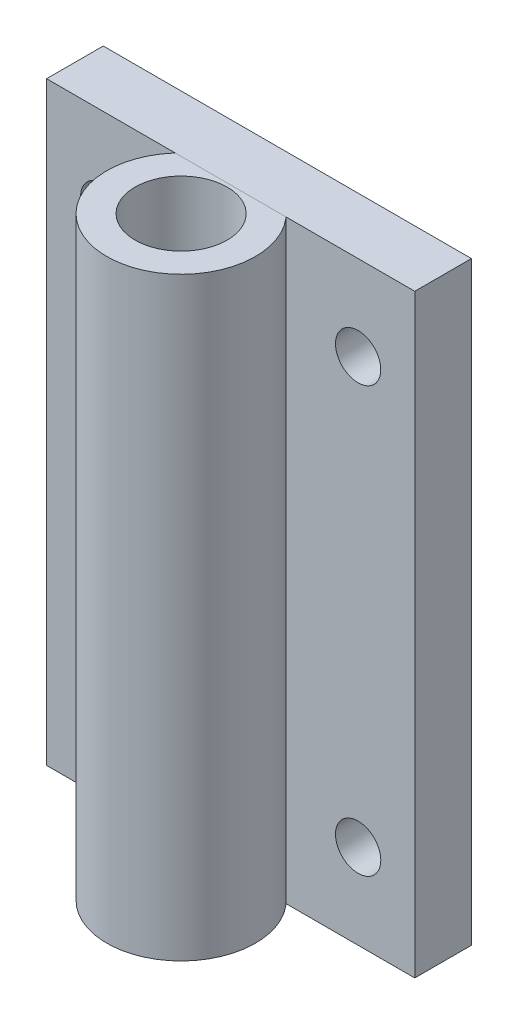
SolidWorks part; units mm, degrees
ref_plane "前视基准面" through (0, 0, 0) normal (0, 0, 1) x (1, 0, 0)
ref_plane "上视基准面" through (0, 0, 0) normal (0, 1, 0) x (1, 0, 0)
ref_plane "右视基准面" through (0, 0, 0) normal (1, 0, 0) x (0, 0, -1)
sketch "草图1" plane through (0, 0, 0) normal (0, 0, 1) x (1, 0, 0)
  line L0 (-13, 0) -> (13, 0) construction
  line L1 (13, -21) -> (-13, -21)
  line L2 (13, -21) -> (13, 21)
  line L3 (13, 21) -> (-13, 21)
  line L4 (-13, -21) -> (-13, 21)
  line L5 (13, -21) -> (-13, 21) construction
  line L6 (13, 21) -> (-13, -21) construction
  line L7 (0, 21) -> (0, -21) construction
  circle A2 centre (-9, 15) radius 1.6
  circle A3 centre (-9, -15) radius 1.6
  circle A4 centre (9, -15) radius 1.6
  circle A5 centre (9, 15) radius 1.6
  point P0 (0, 0)
  dimension "D1" = 3.2
  dimension "D2" = 30
  dimension "D3" = 18
  dimension "D4" = 4
  dimension "D5" = 6
extrude "凸台-拉伸1" add sketch "草图1" along normal blind 4
sketch "草图3" plane through (0, 0, 0) normal (0, 1, 0) x (1, 0, 0)
  line L0 (13, 0) -> (-13, 0) construction
  circle A0 centre (0, -7.5) radius 3.25
  circle A1 centre (0, -7.5) radius 5.25
  dimension "D1" = 6.5
  dimension "D2" = 2
  dimension "D3" = 7.5
extrude "凸台-拉伸2" add sketch "草图3" along normal mid plane 42 separate body
